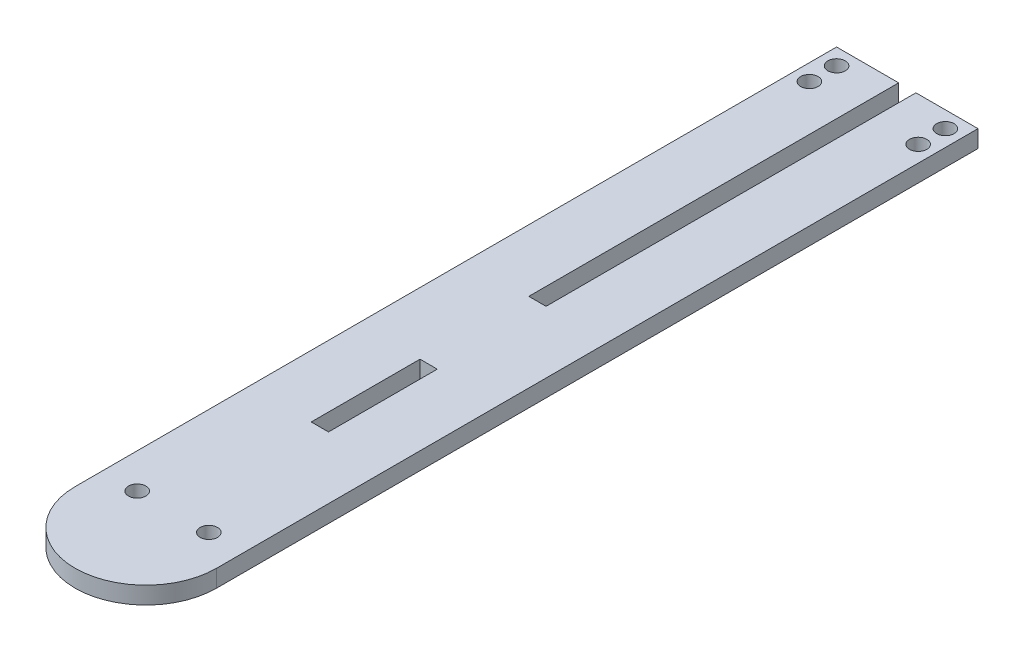
SolidWorks part; units mm, degrees
ref_plane "Front Plane" through (0, 0, 0) normal (0, 0, 1) x (1, 0, 0)
ref_plane "Top Plane" through (0, 0, 0) normal (0, 1, 0) x (1, 0, 0)
ref_plane "Right Plane" through (0, 0, 0) normal (1, 0, 0) x (0, 0, -1)
sketch "Sketch1" plane through (0, 0, 0) normal (0, 1, 0) x (1, 0, 0)
  line L1 (-14.5875, 0) -> (-14.5875, -140)
  line L2 (11.4125, 0) -> (11.4125, -140)
  line L3 (-14.5875, 0) -> (-3.175, 0)
  line L5 (-3.175, 0) -> (-3.175, -68)
  line L6 (-3.175, -68) -> (0, -68)
  line L7 (0, 0) -> (0, -68)
  line L8 (11.4125, 0) -> (0, 0)
  line L10 (-3.175, -88) -> (0, -88)
  line L11 (-3.175, -88) -> (-3.175, -108)
  line L12 (-3.175, -108) -> (0, -108)
  line L13 (0, -88) -> (0, -108)
  arc A0 (-14.5875, -140) -> (11.4125, -140) centre (-1.5875, -140) ccw
  point P6 (-8.8812, 0)
  dimension "D1" = 26
  dimension "D2" = 140
  dimension "D3" = 3.175
  dimension "D4" = 68
  dimension "D5" = 20
  dimension "D6" = 20
extrude "Boss-Extrude1" add sketch "Sketch1" along normal blind 3.175
sketch "Sketch2" plane through (0, 3.175, 0) normal (0, 1, 0) x (1, 0, 0)
  circle A0 centre (5, -135) radius 1.6 construction
  circle A1 centre (-8.175, -135) radius 1.6 construction
  circle A2 centre (5, -135) radius 1.6
  circle A3 centre (-8.175, -135) radius 1.6
extrude "Cut-Extrude1" cut sketch "Sketch2" against normal through all both and the other way through all
sketch "Sketch3" plane through (0, 3.175, 0) normal (0, 1, 0) x (1, 0, 0)
  circle A0 centre (-11.5875, -8) radius 1.6 construction
  circle A1 centre (-11.5875, -3) radius 1.6 construction
  circle A2 centre (8.4125, -8) radius 1.6 construction
  circle A3 centre (8.4125, -3) radius 1.6 construction
  circle A4 centre (-11.5875, -8) radius 1.6
  circle A5 centre (-11.5875, -3) radius 1.6
  circle A6 centre (8.4125, -8) radius 1.6
  circle A7 centre (8.4125, -3) radius 1.6
extrude "Cut-Extrude2" cut sketch "Sketch3" against normal through all both and the other way through all
